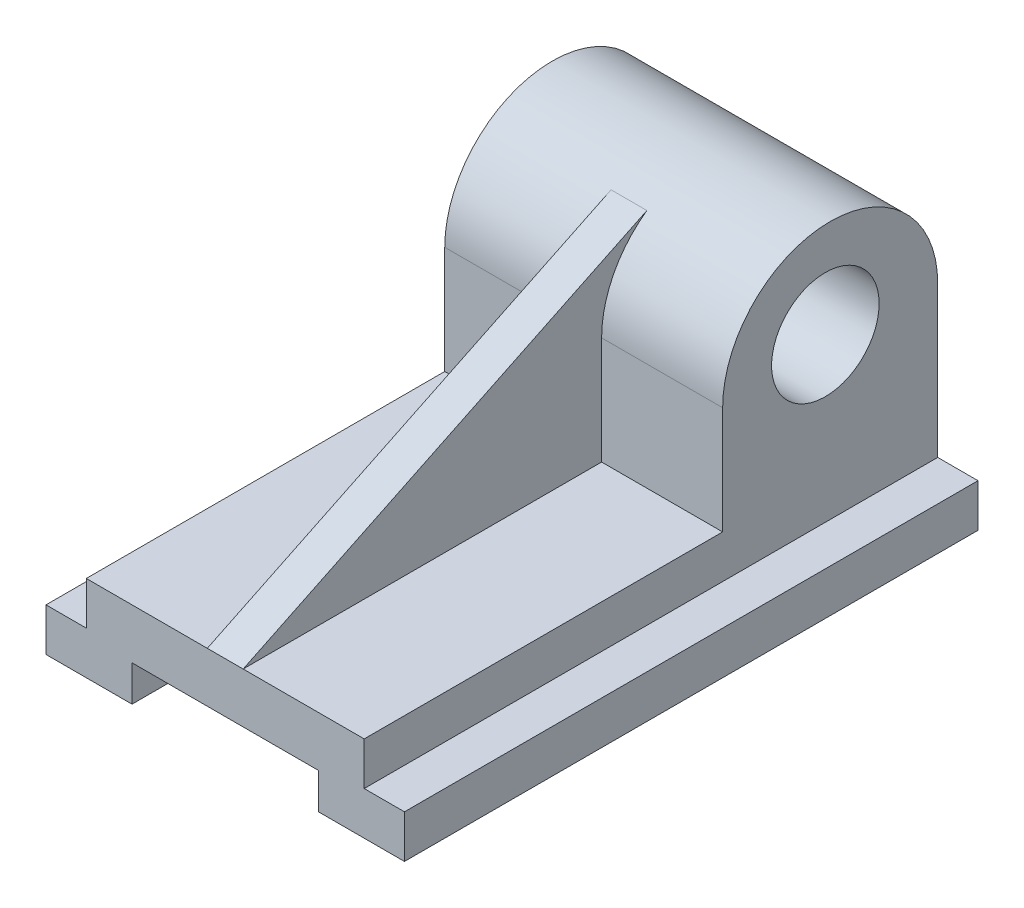
SolidWorks part; units mm, degrees
ref_plane "Front Plane" through (0, 0, 0) normal (0, 0, 1) x (1, 0, 0)
ref_plane "Top Plane" through (0, 0, 0) normal (0, 1, 0) x (1, 0, 0)
ref_plane "Right Plane" through (0, 0, 0) normal (1, 0, 0) x (0, 0, -1)
sketch "Sketch1" plane through (0, 0, 0) normal (0, 0, 1) x (1, 0, 0)
  line L1 (-50, 12) -> (50, 12)
  line L2 (-50, 12) -> (-50, -12)
  line L3 (-50, -12) -> (50, -12)
  line L4 (50, 12) -> (50, -12)
  line L5 (-50, 12) -> (50, -12) construction
  line L6 (-50, -12) -> (50, 12) construction
  point P0 (0, 0)
  dimension "D1" = 100
  dimension "D2" = 24
extrude "Boss-Extrude1" add sketch "Sketch1" along normal blind 160
sketch "Sketch2" plane through (0, 0, 160) normal (0, 0, 1) x (1, 0, 0)
  line L0 (-50, -12) -> (50, -12) construction
  line L1 (-26, -12) -> (26, -12)
  line L2 (-26, -12) -> (-26, -2)
  line L3 (-26, -2) -> (26, -2)
  line L4 (26, -12) -> (26, -2)
  line L5 (-50, 12) -> (-50, -12) construction
  dimension "D1" = 24
  dimension "D2" = 10
  dimension "D3" = 52
extrude "Cut-Extrude1" cut sketch "Sketch2" against normal through all
sketch "Sketch3" plane through (0, 0, 160) normal (0, 0, 1) x (1, 0, 0)
  line L0 (50, 12) -> (-50, 12) construction
  line L1 (50.7637, 12) -> (38.7637, 12)
  line L2 (50.7637, 12) -> (50.7637, 0)
  line L3 (50.7637, 0) -> (38.7637, 0)
  line L4 (38.7637, 12) -> (38.7637, 0)
  dimension "D1" = 12
  dimension "D2" = 12
extrude "Cut-Extrude2" cut sketch "Sketch3" against normal through all
mirror "Mirror1" about plane through (0, 0, 0) normal (1, 0, 0) of "Cut-Extrude2"
sketch "Sketch4" plane through (0, 12, 0) normal (0, 1, 0) x (1, 0, 0)
  line L0 (38.7637, 0) -> (38.7637, -160) construction
  line L1 (-38.7637, 0) -> (38.7637, 0)
  line L2 (-38.7637, 0) -> (-38.7637, -60)
  line L3 (-38.7637, -60) -> (38.7637, -60)
  line L4 (38.7637, 0) -> (38.7637, -60)
  dimension "D1" = 60
extrude "Boss-Extrude2" add sketch "Sketch4" along normal blind 60
fillet "Fillet1" 2 edges at (0, 72, 60) (0, 72, 0) type full round first side face at (0, 42, 60) second side face at (0, 7.6667, 0) middle face at (0, 72, 30)
sketch "Sketch6" plane through (38.7637, 0, 0) normal (1, 0, 0) x (0, 0, -1)
  circle A4 centre (-31.3476, 45.3511) radius 15
  dimension "D1" = 30
extrude "Cut-Extrude3" cut sketch "Sketch6" against normal through all
sketch "Sketch7" plane through (0, 0, 0) normal (1, 0, 0) x (0, 0, -1)
  line L0 (-160, 12) -> (-38.3853, 70.8043)
  arc A2 (0, 42) -> (-60, 42) centre (-30, 42) ccw construction
rib "Rib1" sketch "Sketch7" sketch "Sketch7" thickness 10 extrusion direction parallel to sketch draft on no parameters "D1"=10
